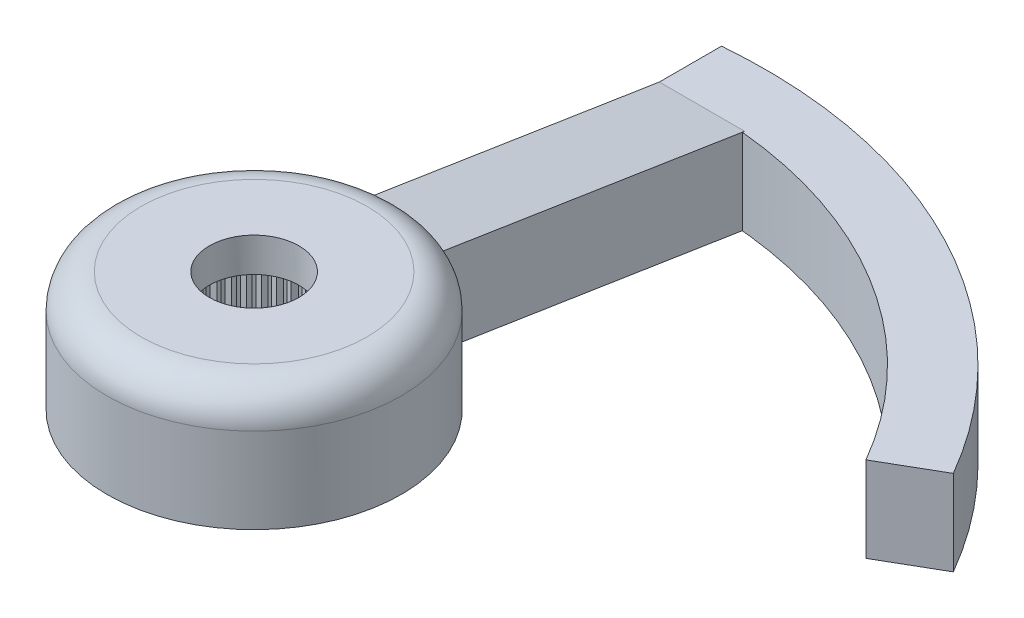
SolidWorks part; units mm, degrees
material "PVC Rígido"
ref_plane "Plano frontal" through (0, 0, 0) normal (0, 0, 1) x (1, 0, 0)
ref_plane "Plano superior" through (0, 0, 0) normal (0, 1, 0) x (1, 0, 0)
ref_plane "Plano direito" through (0, 0, 0) normal (1, 0, 0) x (0, 0, -1)
sketch "Esboço1" plane through (0, 0, 0) normal (0, 1, 0) x (1, 0, 0)
  line L0 (0, 0) -> (-14.05, 0) construction
  line L1 (-14.1591, 1.997) -> (-2.2091, 2.65)
  line L2 (-2.2091, -2.65) -> (-14.1591, -1.997)
  arc A0 (-2.2091, -2.65) -> (-2.2091, 2.65) centre (0, 0) ccw
  arc A1 (-14.1591, 1.997) -> (-14.1591, -1.997) centre (-14.05, 0) ccw
  dimension "D1" = 6.9
  dimension "D2" = 4
  dimension "D3" = 19.5
  dimension "D4" = 5.3
extrude "Ressalto-extrusão1" add sketch "Esboço1" against normal blind 1.4
sketch "Esboço2" plane through (0, -1.4, 0) normal (0, -1, 0) x (1, 0, 0)
  arc A0 (-2.2091, -2.65) -> (-2.2091, 2.65) centre (0, 0) ccw construction
  circle A1 centre (0, 0) radius 3.45
extrude "Ressalto-extrusão2" add sketch "Esboço2" along normal offset from surface (2.4 mm away) 3.8 up to face at (-7.242, 0, 0)
hole_wizard "Furo4" positions "Esboço9" profile "Esboço10" legacy end condition through all
sketch "Esboço9" plane through (0, 0, 0) normal (0, 1, 0) x (1, 0, 0)
  line L1 (-14.45, 0) -> (0, 0) construction
  arc A2 (-14.1591, 1.997) -> (-14.1591, -1.997) centre (-14.05, 0) ccw construction
  point P0 (-14.45, 0)
  point P19 (-16.05, 0)
  dimension "D1" = 1.6
sketch "Esboço10" plane through (-14.45, 0, 0) normal (1, 0, 0) x (0, 0, 1)
  line L0 (0, 0) -> (0, 3.8)
  line L1 (0, 3.8) -> (0.6, 3.8)
  line L2 (0.6, 3.8) -> (0.6, 0)
  line L3 (0.6, 0) -> (0, 0)
  line L4 (0, 110) -> (0, -10) construction
  dimension "Diameter" = 1.2
  dimension "Depth" = 3.8
pattern_linear "Padrão linear1" count 6 spacing 2 along (1, 0, 0) of "Furo4"
hole_wizard "Furo1" positions "Esboço3" profile "Esboço4" legacy
sketch "Esboço3" plane through (0, -3.8, 0) normal (0, -1, 0) x (-1, 0, 0)
  point P0 (0, 0)
sketch "Esboço4" plane through (0, -3.8, 0) normal (1, 0, 0) x (0, 0, -1)
  line L0 (0, 0) -> (0, 2)
  line L1 (0, 2) -> (2.475, 2)
  line L2 (2.475, 2) -> (2.475, 0)
  line L3 (2.475, 0) -> (0, 0)
  line L4 (0, 110) -> (0, -10) construction
  dimension "Diameter" = 4.95
  dimension "Depth" = 2
hole_wizard "Furo2" positions "Esboço5" profile "Esboço6" legacy
sketch "Esboço5" plane through (0, 0, 0) normal (0, 1, 0) x (1, 0, 0)
  point P0 (0, 0)
sketch "Esboço6" plane through (0, 0, 0) normal (1, 0, 0) x (0, 0, 1)
  line L0 (0, 0) -> (0, 1)
  line L1 (0, 1) -> (2.3, 1)
  line L2 (2.3, 1) -> (2.3, 0)
  line L3 (2.3, 0) -> (0, 0)
  line L4 (0, 110) -> (0, -10) construction
  dimension "Diameter" = 4.6
  dimension "Depth" = 1
hole_wizard "Furo3" positions "Esboço7" profile "Esboço8" legacy end condition through all
sketch "Esboço7" plane through (0, 0, 0) normal (0, 1, 0) x (1, 0, 0)
  point P0 (0, 0)
sketch "Esboço8" plane through (0, 0, 0) normal (1, 0, 0) x (0, 0, 1)
  line L0 (0, 0) -> (0, 3.8)
  line L1 (0, 3.8) -> (1.05, 3.8)
  line L2 (1.05, 3.8) -> (1.05, 0)
  line L3 (1.05, 0) -> (0, 0)
  line L4 (0, 110) -> (0, -10) construction
  dimension "Diameter" = 2.1
  dimension "Depth" = 3.8
sketch "Esboço11" plane through (0, -3.8, 0) normal (0, -1, 0) x (1, 0, 0)
  line L0 (-0.0981, 2.4731) -> (0, 2.375)
  line L1 (0, 2.375) -> (0.0981, 2.4731)
  line L2 (0, 0) -> (0, 2.475) construction
  circle A0 centre (0, 0) radius 2.375 construction
  circle A1 centre (0, 0) radius 2.475
  arc A2 (0.0981, 2.4731) -> (-0.0981, 2.4731) centre (0, 0) ccw
  dimension "D3" = 4.75
  dimension "D2" = 0.1
  dimension "D1" = 0
extrude "Ressalto-extrusão3" add sketch "Esboço11" against normal up to surface (2 mm away) up to face at (0, -1.8, 1.05)
pattern_circular "PadrãoCircular1" count 60 over 360 about axis through (0, -1.4, 0) along (0, 1, 0) of "Ressalto-extrusão3"
sketch "Croquis1" plane through (0, -1.4, 0) normal (0, -1, 0) x (1, 0, 0)
  line L0 (-14.1591, 1.997) -> (-2.2091, 2.65) construction
  line L1 (-14.1591, 1.997) -> (-2.2091, 2.65)
  line L2 (-2.2091, -2.65) -> (-14.1591, -1.997) construction
  line L3 (-2.2091, -2.65) -> (-14.1591, -1.997)
  arc A0 (-2.2091, 2.65) -> (-2.2091, -2.65) centre (0, 0) ccw construction
  arc A1 (-14.1591, 1.997) -> (-14.1591, -1.997) centre (-14.05, 0) ccw construction
  arc A2 (-2.2091, 2.65) -> (-2.2091, -2.65) centre (0, 0) ccw
  arc A3 (-14.1591, 1.997) -> (-14.1591, -1.997) centre (-14.05, 0) ccw
extrude "Eliminado brazo anterior" cut sketch "Croquis1" against normal up to next
sketch "Croquis4" plane through (0, 0, 0) normal (0, 1, 0) x (1, 0, 0)
  circle A0 centre (0, 0) radius 3.45 construction
  circle A1 centre (0, 0) radius 3.45
extrude "Cortar-Extruir2" cut sketch "Croquis4" against normal blind 1
fillet "Redondeo1" radius 0.8 1 edges at (0, -1, 3.45)
sketch "Croquis9" plane through (0, 0, 0) normal (1, 0, 0) x (0, 0, -1)
  line L0 (10.5, -4.9) -> (3.45, -3.8)
  line L1 (10.5, -4.9) -> (10.5, -2.9)
  line L2 (3.45, -3.8) -> (3.0334, -3.8)
  line L3 (0, 0) -> (0, -4.9) construction
  line L4 (-10.5, -4.9) -> (10.5, -4.9)
  line L5 (3.45, -1.8) -> (10.5, -2.9)
  line L6 (-3.45, -3.8) -> (3.45, -3.8) construction
  line L10 (3.0334, -3.8) -> (3.0334, -1.8)
  line L11 (3.0334, -1.8) -> (3.45, -1.8)
  point P6 (3.45, -3.8)
  point P8 (3.45, -1.8)
  point P12 (0, -4.9)
  dimension "D1" = 10.5
  dimension "D2" = 1.1
extrude "Saliente-Extruir3" add sketch "Croquis9" along normal blind 1 and the other way blind 1 separate body contours L0 L1 L5 region at (0, -3.3193, -6.7667)
ref_plane "Plano1" through (0, -4.9, 0) normal (0, -1, 0) x (-1, 0, 0)
sketch "Croquis10" plane through (0, -4.9, 0) normal (0, -1, 0) x (-1, 0, 0)
  line L0 (1, 10.4523) -> (1, 10.5)
  line L4 (1, 10.5) -> (1, 11.9583)
  line L5 (0, 0) -> (-12, 0) construction
  line L6 (0, 0) -> (-10.3923, 6) construction
  line L7 (-10.3923, 6) -> (-9.0933, 5.25)
  arc A0 (1, 10.4523) -> (-9.0933, 5.25) centre (0, 0) ccw
  arc A1 (1, 11.9583) -> (-10.3923, 6) centre (0, 0) ccw
  dimension "D1" = 24
  dimension "D2" = 30
extrude "Saliente-Extruir4" add sketch "Croquis10" against normal blind 2
